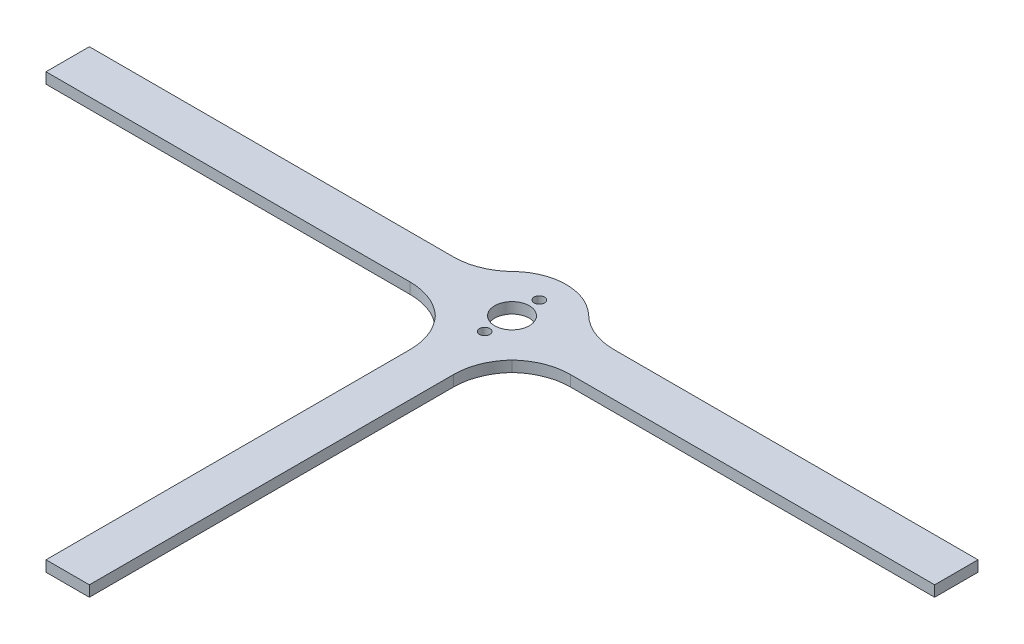
SolidWorks part; units mm, degrees
ref_plane "Front Plane" through (0, 0, 0) normal (0, 0, 1) x (1, 0, 0)
ref_plane "Top Plane" through (0, 0, 0) normal (0, 1, 0) x (1, 0, 0)
ref_plane "Right Plane" through (0, 0, 0) normal (1, 0, 0) x (0, 0, -1)
sketch "Sketch1" plane through (0, 0, 0) normal (0, 1, 0) x (1, 0, 0)
  line L0 (-14.5497, 6.35) -> (-130.175, 6.35)
  line L1 (130.175, -6.35) -> (14.5497, -6.35)
  line L2 (130.175, -6.35) -> (130.175, 6.35)
  line L3 (130.175, 6.35) -> (14.5497, 6.35)
  line L4 (-130.175, -6.35) -> (-130.175, 6.35)
  line L9 (-6.35, -130.175) -> (6.35, -130.175)
  line L12 (6.35, -14.5497) -> (6.35, -130.175)
  line L13 (-6.35, -14.5497) -> (-6.35, -130.175)
  line L14 (-14.5497, -6.35) -> (-130.175, -6.35)
  arc A2 (14.5497, 6.35) -> (-14.5497, 6.35) centre (0, 0) ccw
  arc A3 (-14.5497, -6.35) -> (-6.35, -14.5497) centre (0, 0) ccw
  arc A4 (6.35, -14.5497) -> (14.5497, -6.35) centre (0, 0) ccw
  point P0 (0, 0)
  point P11 (0, -130.175)
  dimension "D5" = 31.75
  dimension "D1" = 260.35
  dimension "D2" = 12.7
  dimension "D3" = 130.175
  dimension "D4" = 12.7
sketch "Screw holes" plane through (0, 0, 0) normal (0, 1, 0) x (1, 0, 0)
  circle A0 centre (0, 8) radius 1.5133
  circle A1 centre (0, -8) radius 1.5133
  circle A2 centre (0, 0) radius 5.08
  dimension "D1" = 16
  dimension "D3" = 3.0266
  dimension "D4" = 10.16
  dimension "D2" = 8
extrude "Boss-Extrude1" add sketch "Sketch1" along normal blind 3.175
extrude "Cut-Extrude1" cut sketch "Screw holes" along normal through all
fillet "Fillet1" radius 17.78 6 edges at (14.5497, 1.5875, 6.35) (14.5497, 1.5875, -6.35) (-14.5497, 1.5875, -6.35) (-6.35, 1.5875, 14.5497) (-14.5497, 1.5875, 6.35) (6.35, 1.5875, 14.5497)
